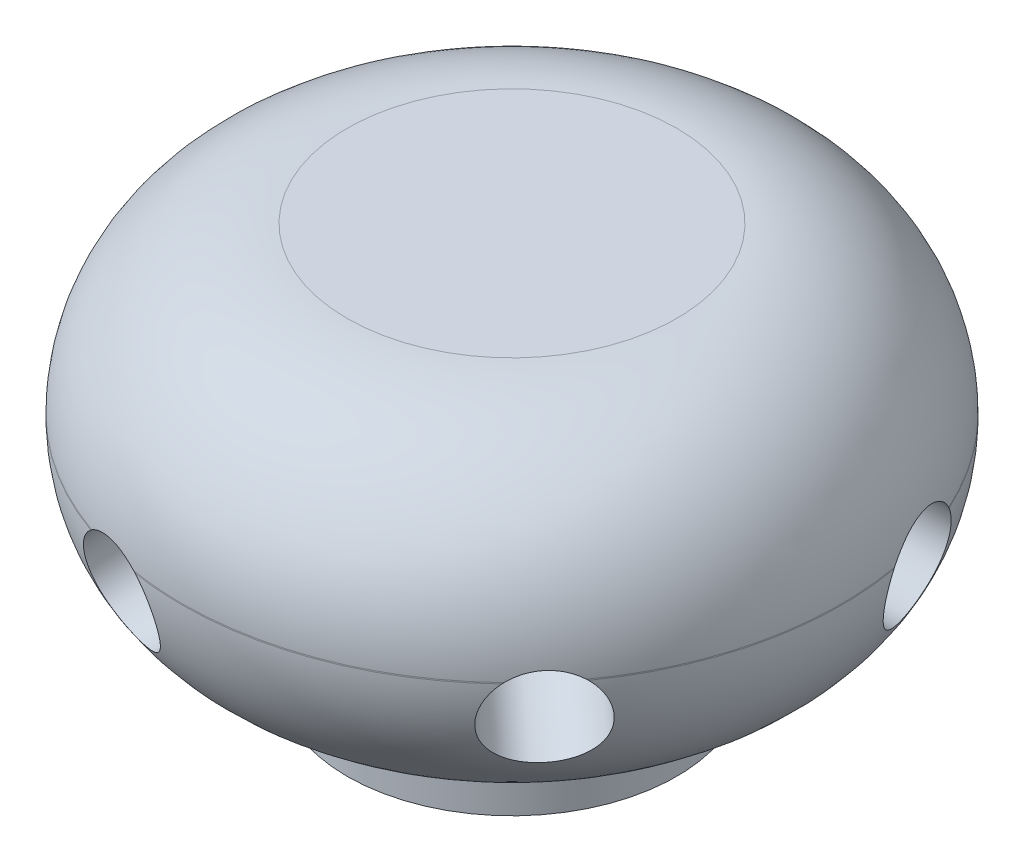
SolidWorks part; units mm, degrees
ref_plane "Front Plane" through (0, 0, 0) normal (0, 0, 1) x (1, 0, 0)
ref_plane "Top Plane" through (0, 0, 0) normal (0, 1, 0) x (1, 0, 0)
ref_plane "Right Plane" through (0, 0, 0) normal (1, 0, 0) x (0, 0, -1)
sketch "Sketch1" plane through (0, 0, 0) normal (0, 1, 0) x (1, 0, 0)
  circle A0 centre (0, 0) radius 10
  dimension "D1" = 20
extrude "base" add sketch "Sketch1" along normal blind 3.0354 and the other way blind 7
ref_axis "6hubaxis" through (0, 5.5, 0) along (0, -1, 0)
ref_plane "Plane1" through (2.6705, -1.0931, 2.7701) normal (-0.6676, 0.2733, -0.6925) x (-0.6559, 0.2243, 0.7208)
sketch "Sketch2" [suppressed] plane through (2.6705, -1.0931, 2.7701) normal (-0.6676, 0.2733, -0.6925) x (-0.6559, 0.2243, 0.7208)
  circle A0 centre (0, 0) radius 1.5 construction
  circle A1 centre (0, 0) radius 1.5
extrude "hole1" [suppressed] cut sketch "Sketch2" against normal through all
pattern_circular "hole1mirror" [suppressed] count 2 over 360 about axis through (0, 5.5, 0) along (0, -1, 0) of bodies 112
ref_plane "Plane2" through (-0.9417, -1.2361, 3.6858) normal (0.2354, 0.309, -0.9215) x (-0.9719, 0.0738, -0.2235)
sketch "Sketch3" plane through (-0.9417, -1.2361, 3.6858) normal (0.2354, 0.309, -0.9215) x (-0.9719, 0.0738, -0.2235)
  circle A0 centre (0, 0) radius 1.5 construction
  circle A1 centre (0, 0) radius 1.5
extrude "hole2" cut sketch "Sketch3" against normal through all
pattern_circular "hole2mirror" count 2 over 360 about axis through (0, 5.5, 0) along (0, -1, 0) of "hole2"
ref_plane "Plane3" through (-3.7178, -1.2361, 0.8061) normal (0.9295, 0.309, -0.2015) x (-0.1912, -0.0636, -0.9795)
sketch "Sketch4" plane through (-3.7178, -1.2361, 0.8061) normal (0.9295, 0.309, -0.2015) x (-0.1912, -0.0636, -0.9795)
  circle A0 centre (0, 0) radius 1.5 construction
  circle A1 centre (0, 0) radius 1.5
extrude "hole3" cut sketch "Sketch4" against normal through all
pattern_circular "hole3mirror" [suppressed] count 2 over 360 about axis through (0, 5.5, 0) along (0, -1, 0) of bodies 117
ref_plane "Plane4" through (3.672, -1.0931, -1.1497) normal (-0.918, 0.2733, 0.2874) x (0.2755, -0.082, 0.9578)
sketch "Sketch5" plane through (3.672, -1.0931, -1.1497) normal (-0.918, 0.2733, 0.2874) x (0.2755, -0.082, 0.9578)
  circle A0 centre (0, 0) radius 1.5 construction
  circle A1 centre (0, 0) radius 1.5
extrude "Cut-Extrude1" cut sketch "Sketch5" against normal through all
ref_plane "Plane5" through (2.8756, -1.2361, 2.4906) normal (-0.7189, 0.309, -0.6227) x (-0.572, 0.2459, 0.7825)
sketch "Sketch6" plane through (2.8756, -1.2361, 2.4906) normal (-0.7189, 0.309, -0.6227) x (-0.572, 0.2459, 0.7825)
  circle A0 centre (0, 0) radius 1.5 construction
  circle A1 centre (0, 0) radius 1.5
extrude "Cut-Extrude2" cut sketch "Sketch6" against normal through all
ref_plane "Plane6" through (-2.6705, -1.0931, -2.7701) normal (0.6676, 0.2733, 0.6925) x (0.7445, -0.2451, -0.621)
sketch "Sketch7" plane through (-2.6705, -1.0931, -2.7701) normal (0.6676, 0.2733, 0.6925) x (0.7445, -0.2451, -0.621)
  circle A0 centre (0, 0) radius 1.5 construction
  circle A1 centre (0, 0) radius 1.5
extrude "Cut-Extrude3" cut sketch "Sketch7" against normal through all
fillet "Fillet1" radius 5 2 edges at (0, -7, 10) (0, 3.0354, 10)
sketch "Sketch8" plane through (0, -7, 0) normal (0, -1, 0) x (1, 0, 0)
  circle A0 centre (0, 0) radius 5
extrude "Boss-Extrude1" add sketch "Sketch8" along normal blind 2
